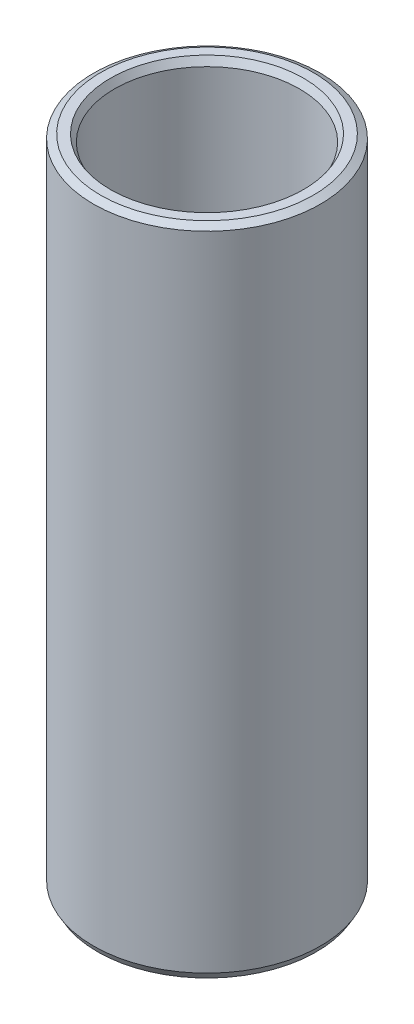
SolidWorks part; units mm, degrees
ref_plane "Front Plane" through (0, 0, 0) normal (0, 0, 1) x (1, 0, 0)
ref_plane "Top Plane" through (0, 0, 0) normal (0, 1, 0) x (1, 0, 0)
ref_plane "Right Plane" through (0, 0, 0) normal (1, 0, 0) x (0, 0, -1)
sketch "Sketch1" plane through (0, 0, 0) normal (0, 1, 0) x (1, 0, 0)
  circle A0 centre (0, 0) radius 32.5
  dimension "SLEEVE_OD" = 65
extrude "Boss-Extrude1" add sketch "Sketch1" along normal blind 187.2198
sketch "Sketch2" plane through (0, 0, 0) normal (0, 1, 0) x (1, 0, 0)
  circle A0 centre (0, 0) radius 26.4687
  dimension "BORE_D" = 52.9374
extrude "Cut-Extrude1" cut sketch "Sketch2" along normal through all
chamfer "Chamfer1" distance 1.1807 angle 60 4 edges at (0, 187.2198, 26.4687) (0, 0, 26.4687) (0, 0, 32.5) (0, 187.2198, 32.5) first distance on face at (0, 187.2198, 26.4687) first distance on face at (0, 0, 26.4687) first distance on face at (0, 187.2198, 32.5)
